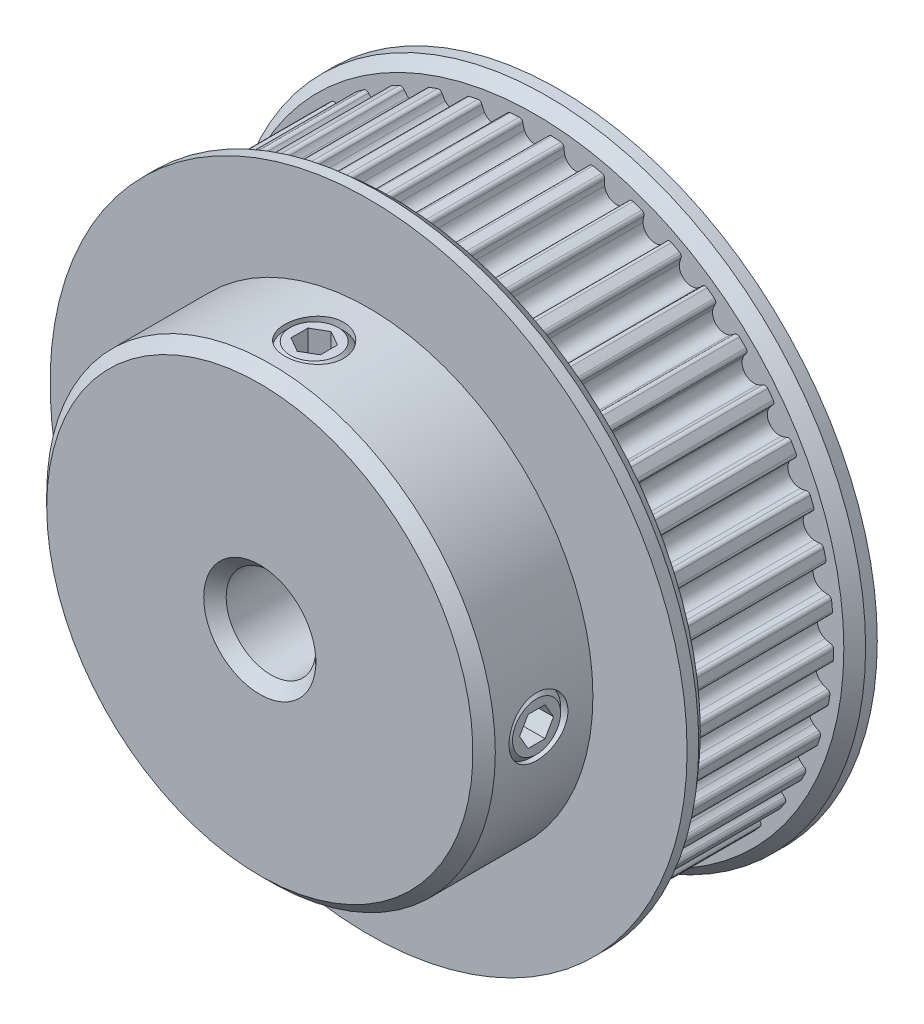
SolidWorks part; units mm, degrees
ref_plane "Front Plane" through (0, 0, 0) normal (0, 0, 1) x (1, 0, 0)
ref_plane "Top Plane" through (0, 0, 0) normal (0, 1, 0) x (1, 0, 0)
ref_plane "Right Plane" through (0, 0, 0) normal (1, 0, 0) x (0, 0, -1)
sketch "Sketch1" plane through (0, 0, 0) normal (0, 0, 1) x (1, 0, 0)
  line L1 (-2.8082, 19.9675) -> (2.8082, 19.9675) construction
  line L4 (0, 0) -> (0, 19.9675) construction
  line L5 (0, 19.9675) -> (0, 22.0837) construction
  line L6 (0, 21.4885) -> (2.9927, 21.2791) construction
  line L7 (2.9927, 21.2791) -> (4.3043, 21.0946) construction
  line L8 (2.9927, 21.2791) -> (2.8082, 19.9675) construction
  line L9 (-2.9927, 21.2791) -> (-2.8082, 19.9675) construction
  line L10 (-2.9396, 20.9018) -> (-3.1704, 22.5425)
  line L11 (-3.1704, 22.5425) -> (3.1704, 22.5425)
  line L12 (3.1704, 22.5425) -> (2.9396, 20.9018)
  circle A0 centre (0, 0) radius 21.4885 construction
  circle A1 centre (0, 0) radius 22.5425 construction
  circle A2 centre (0, 0) radius 21.1075 construction
  arc A3 (-0.7739, 20.4659) -> (0.7739, 20.4659) centre (0, 20.8175) ccw
  arc A4 (-0.7739, 20.4659) -> (-0.8924, 20.8642) centre (0.61, 21.0946) cw
  arc A5 (-2.9396, 20.9018) -> (-1.1532, 21.076) centre (0, 0) cw
  arc A6 (-0.8924, 20.8642) -> (-1.1532, 21.076) centre (-1.1396, 20.8263) ccw
  arc A7 (2.9396, 20.9018) -> (1.1532, 21.076) centre (0, 0) ccw
  arc A8 (0.8924, 20.8642) -> (1.1532, 21.076) centre (1.1396, 20.8263) cw
  arc A9 (0.7739, 20.4659) -> (0.8924, 20.8642) centre (-0.61, 21.0946) ccw
  point P6 (0, 20.9083)
  point P11 (0, 21.4885)
  point P13 (0, 22.5425)
  point P14 (0, 21.1075)
  dimension "D1" = 1.1753
  dimension "D2" = 0.5952
sketch "Sketch2" plane through (0, 0, 0) normal (1, 0, 0) x (0, 0, -1)
  line L0 (-10.58, 3.175) -> (10.58, 3.175)
  line L1 (-10.58, 3.175) -> (-10.58, 15.875)
  line L2 (-10.58, 15.875) -> (-2.88, 15.875)
  line L3 (-2.88, 15.875) -> (-2.88, 22.5425)
  line L4 (-2.88, 22.5425) -> (-1.23, 22.5425) construction
  line L5 (-1.23, 22.5425) -> (-1.23, 21.1075) construction
  line L6 (-1.23, 21.1075) -> (8.93, 21.1075)
  line L7 (8.93, 21.1075) -> (8.93, 22.5425) construction
  line L8 (8.93, 22.5425) -> (10.58, 22.5425) construction
  line L9 (10.58, 22.5425) -> (10.58, 3.175)
  line L10 (-10.58, 0) -> (10.58, 0) construction
  line L11 (9.755, 22.5425) -> (8.93, 21.825)
  line L12 (-1.23, 21.825) -> (-2.055, 22.5425)
  line L13 (-2.88, 22.5425) -> (-2.055, 22.5425)
  line L14 (-1.23, 21.825) -> (-1.23, 21.1075)
  line L15 (8.93, 21.1075) -> (8.93, 21.825)
  line L16 (9.755, 22.5425) -> (10.58, 22.5425)
  arc A0 (-1.23, 21.825) -> (-2.055, 22.5425) centre (-1.9545, 21.825) ccw construction
  arc A1 (8.93, 21.825) -> (9.755, 22.5425) centre (9.6545, 21.825) cw construction
  point P12 (-1.23, 21.825)
  point P14 (-2.055, 22.5425)
  point P20 (8.93, 21.825)
  point P21 (9.755, 22.5425)
  point P25 (8.93, 0)
  point P26 (-1.23, 0)
revolve "Revolve1" add sketch "Sketch2" angle 360 mid plane about L10
sketch "Sketch3" plane through (0, 0, 0) normal (0, 0, 1) x (1, 0, 0)
  line L6 (3.1704, 22.5425) -> (-3.1704, 22.5425)
  line L7 (2.9396, 20.9018) -> (3.1704, 22.5425)
  line L8 (-3.1704, 22.5425) -> (-2.9396, 20.9018)
  line L9 (3.1704, 22.5425) -> (-3.1704, 22.5425)
  line L10 (2.9396, 20.9018) -> (3.1704, 22.5425)
  line L11 (-3.1704, 22.5425) -> (-2.9396, 20.9018)
  arc A8 (2.9396, 20.9018) -> (1.1532, 21.076) centre (0, 0) ccw
  arc A9 (1.1532, 21.076) -> (0.8924, 20.8642) centre (1.1396, 20.8263) ccw
  arc A10 (0.7739, 20.4659) -> (0.8924, 20.8642) centre (-0.61, 21.0946) ccw
  arc A11 (-0.7739, 20.4659) -> (0.7739, 20.4659) centre (0, 20.8175) ccw
  arc A12 (-0.8924, 20.8642) -> (-0.7739, 20.4659) centre (0.61, 21.0946) ccw
  arc A13 (-0.8924, 20.8642) -> (-1.1532, 21.076) centre (-1.1396, 20.8263) ccw
  arc A14 (-1.1532, 21.076) -> (-2.9396, 20.9018) centre (0, 0) ccw
  arc A15 (2.9396, 20.9018) -> (1.1532, 21.076) centre (0, 0) ccw
  arc A16 (1.1532, 21.076) -> (0.8924, 20.8642) centre (1.1396, 20.8263) ccw
  arc A17 (0.7739, 20.4659) -> (0.8924, 20.8642) centre (-0.61, 21.0946) ccw
  arc A18 (-0.7739, 20.4659) -> (0.7739, 20.4659) centre (0, 20.8175) ccw
  arc A19 (-0.8924, 20.8642) -> (-0.7739, 20.4659) centre (0.61, 21.0946) ccw
  arc A20 (-0.8924, 20.8642) -> (-1.1532, 21.076) centre (-1.1396, 20.8263) ccw
  arc A21 (-1.1532, 21.076) -> (-2.9396, 20.9018) centre (0, 0) ccw
  dimension "D1" = 0
extrude "Cut-Extrude1" cut sketch "Sketch3" against normal up to vertex (8.93 mm away) from vertex up to point (0, 21.1075, -8.93) starting at point (0, 21.1075, 1.23)
pattern_circular "CirPattern1" count 45 over 360 about axis through (0, 0, 10.58) along (0, 0, 1) of "Cut-Extrude1"
sketch "Sketch4" plane through (0, 0, 0) normal (1, 0, 0) x (0, -1, 0)
  line L0 (0, -2.88) -> (0, -10.58) construction
  line L1 (-15.875, -2.88) -> (15.875, -2.88) construction
  line L2 (-15.875, -10.58) -> (15.875, -10.58) construction
  circle A0 centre (0, -6.73) radius 2.0828
extrude "Cut-Extrude2" cut sketch "Sketch4" along normal through all
ref_plane "Plane1" through (0, 0, 6.73) normal (0, 0, 1) x (1, 0, 0)
sketch "Sketch5" plane through (0, 0, 6.73) normal (0, 0, 1) x (1, 0, 0)
  line L0 (0, 0.1664) -> (0, 15.875) construction
  line L1 (3.175, -1.7018) -> (3.175, 0)
  line L2 (3.556, -2.0828) -> (15.3568, -2.0828)
  line L3 (3.175, 0) -> (15.875, 0) construction
  line L4 (3.175, 0) -> (15.7378, 0)
  line L5 (15.7378, 0) -> (15.7378, -1.7018)
  line L6 (3.556, -2.0828) -> (3.175, -1.7018)
  line L7 (15.7378, -1.7018) -> (15.3568, -2.0828)
  circle A0 centre (0, 0) radius 15.875 construction
  circle A1 centre (0, 0) radius 3.175 construction
  point P2 (3.175, -2.0828)
  point P11 (15.7378, -2.0828)
revolve "Revolve2" add sketch "Sketch5" angle 360 mid plane about L4
sketch "Sketch6" plane through (15.7378, 5.3841, 0) normal (-1, 0, 0) x (0, -1, 0)
  line L1 (5.3841, 7.9325) -> (4.3427, 7.3313)
  line L2 (4.3427, 7.3313) -> (4.3427, 6.1287)
  line L3 (4.3427, 6.1287) -> (5.3841, 5.5275)
  line L4 (5.3841, 5.5275) -> (6.4255, 6.1287)
  line L5 (6.4255, 6.1287) -> (6.4255, 7.3313)
  line L6 (6.4255, 7.3313) -> (5.3841, 7.9325)
  circle A0 centre (5.3841, 6.73) radius 1.0414 construction
  dimension "D1" = 2.0828
extrude "Cut-Extrude3" cut sketch "Sketch6" along normal blind 1.5621
pattern_circular "CirPattern2" count 2 over 90 about axis through (0, 0, 10.58) along (0, 0, 1) of "Cut-Extrude2", "Revolve2", "Cut-Extrude3"
chamfer "Chamfer1" distance 0.7938 angle 45 2 edges at (3.175, 0, 10.58) (15.875, 0, 10.58)
ref_axis "Center Axis 1" through (0, 0, -10.58) along (0, 0, 1)
ref_plane "Contact Plane 1" through (0, 0, 10.58) normal (0, 0, 1) x (1, 0, 0)
ref_plane "Contact Plane 2" through (0, 0, -10.58) normal (0, 0, -1) x (-1, 0, 0)
ref_axis "Axis1" through (0, 0, -10.58) along (0, 0, 1)
equation "\"D2@Sketch1\" = \"D1@Sketch1\"/2"
equation "\"D1@Sketch6\" = \"Set Screw@Sketch4\" / 2"
equation "\"D1@Cut-Extrude3\" = \"D1@Sketch6\"*.75"
equation "\"D1@Chamfer1\"=\"Hub Dia@Sketch2\"*.025"
